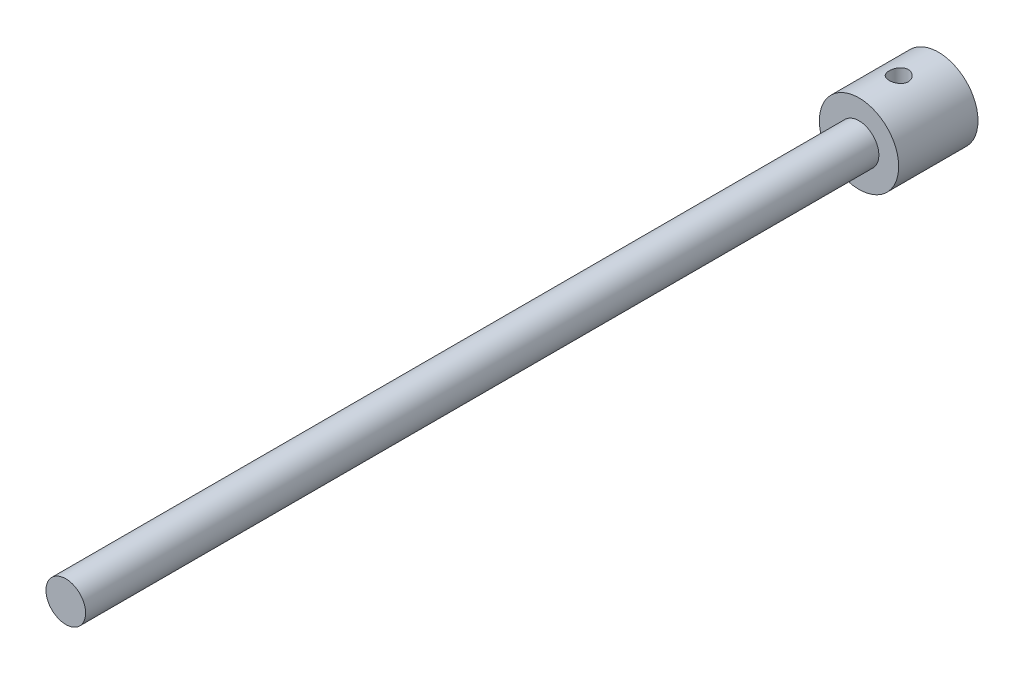
SolidWorks part; units mm, degrees
ref_plane "Front Plane" through (0, 0, 0) normal (0, 0, 1) x (1, 0, 0)
ref_plane "Top Plane" through (0, 0, 0) normal (0, 1, 0) x (1, 0, 0)
ref_plane "Right Plane" through (0, 0, 0) normal (1, 0, 0) x (0, 0, -1)
sketch "Sketch1" plane through (0, 0, 0) normal (0, 0, 1) x (1, 0, 0)
  circle A0 centre (0, 0) radius 25
  circle A1 centre (0, 0) radius 12.5
  dimension "D1" = 50
  dimension "D2" = 25
extrude "Boss-Extrude1" add sketch "Sketch1" along normal blind 50 contours A0
extrude "Boss-Extrude2" add sketch "Sketch1<3>" along normal blind 550 contours A1
sketch "Sketch1<3>" plane through (0, 0, 0) normal (0, 0, 1) x (1, 0, 0) same geometry as "Sketch1"
cosmetic thread "Cosmetic Thread1" parameters "D1"=5, "D2"=24
cosmetic thread "Cosmetic Thread2" parameters "D1"=5, "D2"=24
sketch "Sketch2" plane through (0, 0, 0) normal (0, 1, 0) x (1, 0, 0)
  line L0 (25, 0) -> (-25, 0) construction
  circle A0 centre (0, -25) radius 6
  point P5 (0, 0)
  dimension "D1" = 12
  dimension "D2" = 25
extrude "Cut-Extrude1" cut sketch "Sketch2" against normal through all both and the other way through all
